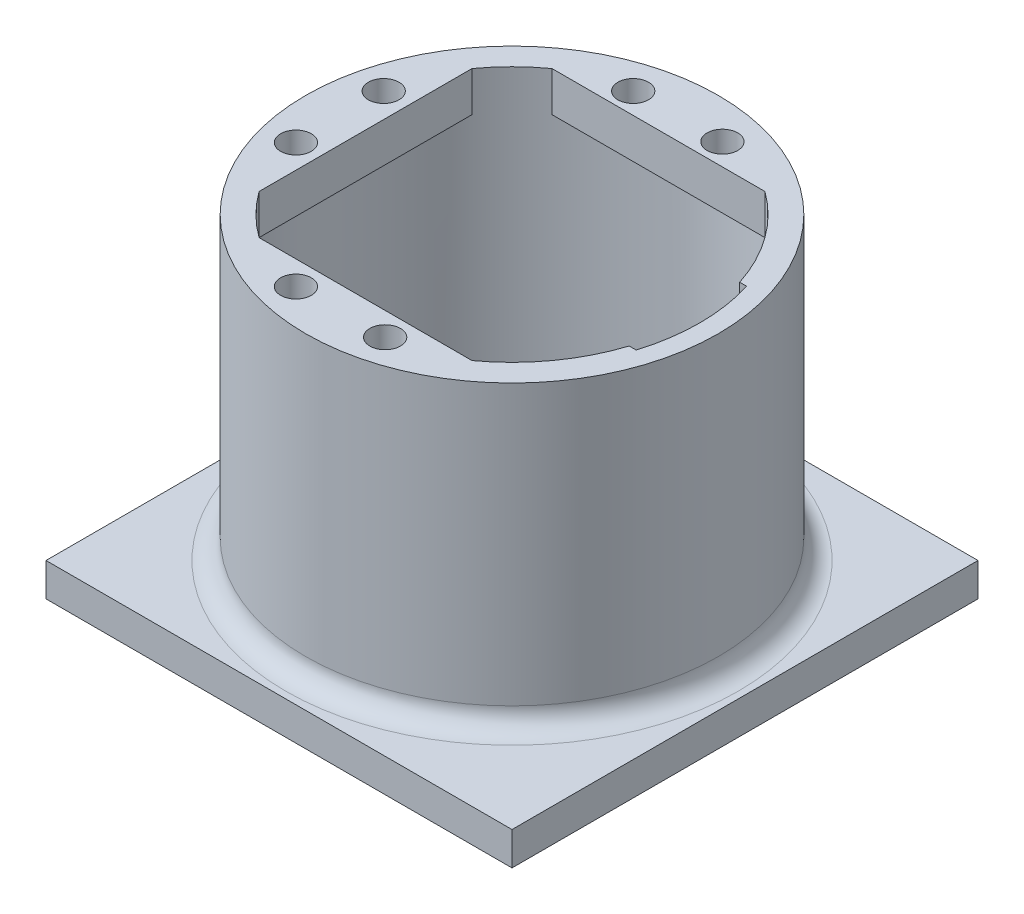
SolidWorks part; units mm, degrees
ref_plane "Front Plane" through (0, 0, 0) normal (0, 0, 1) x (1, 0, 0)
ref_plane "Top Plane" through (0, 0, 0) normal (0, 1, 0) x (1, 0, 0)
ref_plane "Right Plane" through (0, 0, 0) normal (1, 0, 0) x (0, 0, -1)
sketch "Sketch1" plane through (0, 0, 0) normal (0, 1, 0) x (1, 0, 0)
  line L0 (25.9027, -8.3) -> (26.9509, -8.3)
  line L1 (25.9027, 8.3) -> (26.9509, 8.3)
  circle A0 centre (0, 0) radius 31
  arc A1 (25.9027, 8.3) -> (25.9027, -8.3) centre (0, 0) ccw
  arc A2 (26.9509, -8.3) -> (26.9509, 8.3) centre (0, 0) ccw
extrude "Boss-Extrude1" add sketch "Sketch1" against normal blind 50
sketch "Sketch2" plane through (0, 0, 0) normal (0, 1, 0) x (1, 0, 0)
  line L1 (15.995, -22) -> (-15.995, -22)
  line L2 (-15.995, 22) -> (15.995, 22)
  line L3 (-22, -15.995) -> (-22, 15.995)
  line L4 (22, 15.995) -> (22, -15.995) [skipped]
  arc A0 (15.995, 22) -> (-15.995, 22) centre (0, 0) ccw
  arc A2 (-15.995, -22) -> (15.995, -22) centre (0, 0) ccw
  arc A3 (-22, 15.995) -> (-22, -15.995) centre (0, 0) ccw
  arc A4 (22, -15.995) -> (22, 15.995) centre (0, 0) ccw [skipped]
  point P13 (0, 0)
  dimension "D1" = 4
extrude "Boss-Extrude2" add sketch "Sketch2" against normal blind 6
sketch "Sketch3" plane through (0, 0, 0) normal (0, 1, 0) x (1, 0, 0)
  circle A0 centre (-25.7069, 6.4346) radius 2.3
  circle A2 centre (-32.5343, 4.4837) radius 2.3 [skipped]
  circle A3 centre (-25.597, -6.8587) radius 2.3
  circle A4 centre (-6.9686, 25.173) radius 2.3
  circle A5 centre (6.3248, 25.2829) radius 2.3
  circle A8 centre (6.4346, -25.4872) radius 2.3
  circle A9 centre (-6.8587, -25.597) radius 2.3
  circle A10 centre (25.0631, 6.5445) radius 2.3 [skipped]
  circle A11 centre (25.173, -6.7488) radius 2.3 [skipped]
  point P5 (-25.4802, -7.2809)
  point P8 (-25.4802, -7.2809)
  point P13 (0, 0)
  point P26 (-0.267, -0.1571)
  dimension "D1" = 2
  dimension "D2" = 2
  dimension "D3" = 4
extrude "Cut-Extrude1" cut sketch "Sketch3" against normal blind 4
sketch "Sketch5" plane through (0, -50, 0) normal (0, -1, 0) x (1, 0, 0)
  line L1 (-35, -35) -> (35, -35)
  line L2 (-35, -35) -> (-35, 35)
  line L3 (-35, 35) -> (35, 35)
  line L4 (35, -35) -> (35, 35)
  line L5 (-35, -35) -> (35, 35) construction
  line L6 (-35, 35) -> (35, -35) construction
  circle A0 centre (0, 0) radius 31
  point P0 (0, 0)
extrude "Boss-Extrude3" add sketch "Sketch5" against normal blind 5
fillet "Fillet1" radius 3 1 edges at (0, -45, 31)
